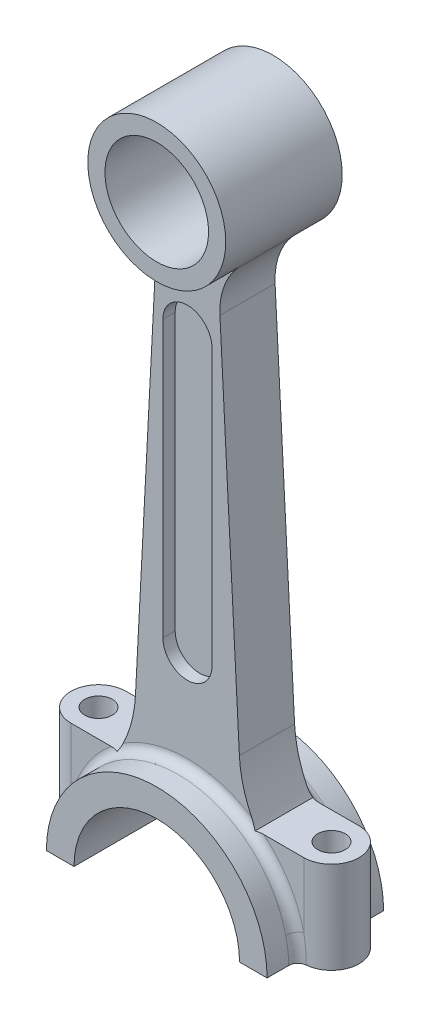
SolidWorks part; units mm, degrees
ref_plane "Front Plane" through (0, 0, 0) normal (0, 0, 1) x (1, 0, 0)
ref_plane "Top Plane" through (0, 0, 0) normal (0, 1, 0) x (1, 0, 0)
ref_plane "Right Plane" through (0, 0, 0) normal (1, 0, 0) x (0, 0, -1)
sketch "Sketch1" plane through (0, 0, 0) normal (0, 0, 1) x (1, 0, 0)
  line L0 (0, 0) -> (0, -201.2) construction
  line L1 (-10, -20.1556) -> (-17.8497, -169.9368)
  line L2 (10, -20.1556) -> (17.8497, -169.9368)
  line L3 (-27, -201.2) -> (-36, -201.2)
  line L4 (27, -201.2) -> (36, -201.2)
  circle A0 centre (0, 0) radius 16.9
  circle A1 centre (0, 0) radius 22.5
  circle A2 centre (0, -201.2) radius 36
  circle A3 centre (0, -201.2) radius 27
  dimension "D1" = 72
  dimension "D2" = 54
  dimension "D4" = 45
  dimension "D5" = 33.8
  dimension "D3" = 201.2
  dimension "D6" = 20
  dimension "D7" = 6
extrude "Boss-Extrude1" add sketch "Sketch1" along normal mid plane 38 contours A0 A1 | L0 A2 L3 A3 | A2 L0 A3 L4 region at (-4.9903, -21.2865, 0) region at (20.1899, -181.0101, 0) region at (-20.1899, -181.0101, 0)
extrude "Boss-Extrude2" add sketch "Sketch1<3>" along normal mid plane 18 contours L0 A1 L1 A2 | A1 L0 A2 L2 region at (7.1843, -100.8455, 0) region at (-7.1843, -100.8455, 0)
sketch "Sketch1<3>" plane through (0, 0, 0) normal (0, 0, 1) x (1, 0, 0) same geometry as "Sketch1"
sketch "Sketch2" plane through (0, 0, 9) normal (0, 0, 1) x (1, 0, 0)
  line L0 (0, 0) -> (0, -174.2) construction
  line L1 (0, -132.1) -> (0, -42.1) construction
  line L2 (-8, -132.1) -> (-8, -42.1)
  line L3 (8, -132.1) -> (8, -42.1)
  circle A0 centre (0, -201.2) radius 27 construction
  arc A1 (-8, -132.1) -> (8, -132.1) centre (0, -132.1) ccw
  arc A2 (8, -42.1) -> (-8, -42.1) centre (0, -42.1) ccw
  point P8 (0, -87.1)
  dimension "D2" = 8
  dimension "D1" = 90
extrude "Cut-Extrude1" cut sketch "Sketch2" against normal blind 4
mirror "Mirror1" about plane through (0, 0, 0) normal (0, 0, 1) of "Cut-Extrude1"
ref_plane "Plane1" through (0, -171.2, 0) normal (0, -1, 0) x (-1, 0, 0)
fillet "Fillet2" radius 40 2 edges at (17.8497, -169.9368, 0) (-17.8497, -169.9368, 0)
fillet "Fillet3" radius 22.5 2 edges at (10, -20.1556, 0) (-10, -20.1556, 0)
sketch "Sketch3" plane through (0, -171.2, 0) normal (0, -1, 0) x (-1, 0, 0)
  line L0 (-38, 0) -> (38, 0) construction
  line L1 (-38, 9) -> (38, 9)
  line L2 (-38, -9) -> (38, -9)
  arc A0 (-38, 9) -> (-38, -9) centre (-38, 0) ccw
  arc A1 (38, -9) -> (38, 9) centre (38, 0) ccw
  circle A2 centre (38, 0) radius 4.5
  circle A3 centre (-38, 0) radius 4.5
  point P2 (0, 0)
  dimension "D2" = 9
  dimension "D3" = 9
  dimension "D1" = 76
extrude "Boss-Extrude3" add sketch "Sketch3" along normal up to surface (30 mm away) up to face at (-31.5, -201.2, 0)
sketch "Sketch4" plane through (0, 0, 9) normal (0, 0, 1) x (1, 0, 0)
  arc A0 (27, -201.2) -> (-27, -201.2) centre (0, -201.2) ccw construction
  arc A1 (27, -201.2) -> (-27, -201.2) centre (0, -201.2) ccw
extrude "Cut-Extrude2" cut sketch "Sketch4" against normal through all and the other way through all
fillet "Fillet4" radius 3 2 edges at (0, -165.2, -9) (0, -165.2, 9)
